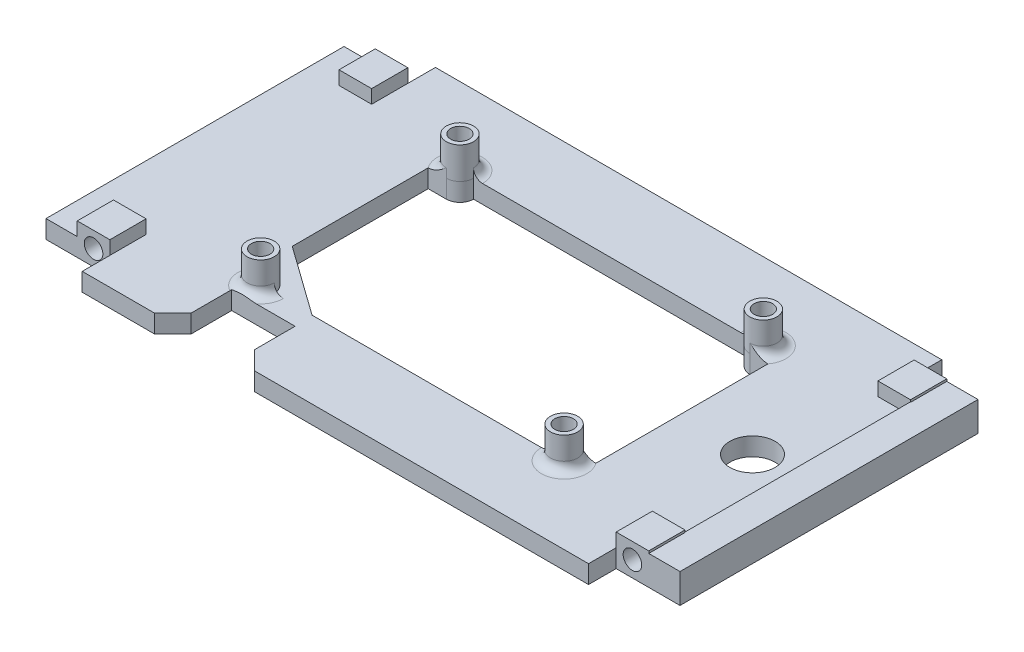
SolidWorks part; units mm, degrees
ref_plane "Front Plane" through (0, 0, 0) normal (0, 0, 1) x (1, 0, 0)
ref_plane "Top Plane" through (0, 0, 0) normal (0, 1, 0) x (1, 0, 0)
ref_plane "Right Plane" through (0, 0, 0) normal (1, 0, 0) x (0, 0, -1)
sketch "Sketch1" plane through (0, 0, 0) normal (0, 1, 0) x (1, 0, 0)
  line L0 (-70, -32.9) -> (-70, 32.9)
  line L1 (-70, -40) -> (70, -40) construction
  line L2 (-70, -40) -> (-70, 40) construction
  line L3 (-70, 40) -> (70, 40) construction
  line L4 (70, -40) -> (70, 40) construction
  line L5 (-70, -40) -> (70, 40) construction
  line L6 (-70, 40) -> (70, -40) construction
  line L7 (-70, 32.9) -> (-55.9, 32.9)
  line L8 (-55.9, 32.9) -> (-55.9, 40)
  line L9 (-55.9, 40) -> (55.9, 40)
  line L10 (55.9, 40) -> (55.9, 32.9)
  line L11 (55.9, 32.9) -> (70, 32.9)
  line L12 (70, 32.9) -> (70, -32.9)
  line L13 (70, -32.9) -> (55.9, -32.9)
  line L14 (55.9, -32.9) -> (55.9, -40)
  line L15 (55.9, -40) -> (-55.9, -40)
  line L16 (-55.9, -40) -> (-55.9, -32.9)
  line L17 (-55.9, -32.9) -> (-70, -32.9)
  point P0 (0, 0)
  dimension "D1" = 140
  dimension "D2" = 80
  dimension "D3" = 7.1
  dimension "D4" = 14.1
extrude "Boss-Extrude1" add sketch "Sketch1" along normal blind 4
sketch "Sketch3" plane through (0, 4, 0) normal (0, 1, 0) x (1, 0, 0)
  line L1 (-33.5, 22) -> (33.5, 22) construction
  line L2 (-33.5, 22) -> (-33.5, -22) construction
  line L3 (-33.5, -22) -> (33.5, -22) construction
  line L4 (33.5, 22) -> (33.5, -22) construction
  line L5 (-33.5, 22) -> (33.5, -22) construction
  line L6 (-33.5, -22) -> (33.5, 22) construction
  circle A0 centre (-33.5, -22) radius 3
  circle A1 centre (33.5, -22) radius 3
  circle A2 centre (33.5, 22) radius 3
  circle A3 centre (-33.5, 22) radius 3
  point P0 (0, 0)
  dimension "D4" = 6
  dimension "D1" = 67
  dimension "D2" = 44
sketch "Sketch2" plane through (0, 4, 0) normal (0, 1, 0) x (1, 0, 0)
  line L0 (-33.5, 19) -> (-30.5, 19)
  line L5 (-30.5, -22) -> (30.5, -22)
  line L6 (-33.5, -19) -> (-33.5, 19)
  line L7 (-30.5, 22) -> (30.5, 22)
  line L8 (33.5, -19) -> (33.5, 19)
  line L9 (-33.5, -22) -> (33.5, 22) construction
  line L10 (-33.5, 22) -> (33.5, -22) construction
  line L11 (-30.5, 19) -> (-30.5, 22)
  line L12 (30.5, 22) -> (30.5, 19)
  line L13 (30.5, 19) -> (33.5, 19)
  line L14 (33.5, -19) -> (30.5, -19)
  line L15 (30.5, -19) -> (30.5, -22)
  line L16 (-30.5, -22) -> (-30.5, -19)
  line L17 (-30.5, -19) -> (-33.5, -19)
  line L18 (33.5, -22) -> (-33.5, -22) construction
  line L19 (-33.5, -22) -> (-33.5, 22) construction
  line L20 (-33.5, 22) -> (33.5, 22) construction
  line L21 (33.5, 22) -> (33.5, -22) construction
  point P0 (0, 0)
  point P1 (0, 0)
  dimension "D1" = 3
extrude "Cut-Extrude1" cut sketch "Sketch2" against normal through all
extrude "Boss-Extrude2" add sketch "Sketch3" along normal blind 7
sketch "Sketch4" plane through (0, 11, 0) normal (0, 1, 0) x (1, 0, 0)
  circle A0 centre (-33.5, 22) radius 2.05
  circle A1 centre (33.5, 22) radius 2.05
  circle A2 centre (33.5, -22) radius 2.05
  circle A3 centre (-33.5, -22) radius 2.05
  dimension "D1" = 4.1
extrude "Cut-Extrude2" cut sketch "Sketch4" against normal through all and the other way through all
sketch "Sketch5" plane through (0, 4, 0) normal (0, 1, 0) x (1, 0, 0)
  line L0 (-33.5, -19) -> (-30.5, -19) construction
  line L1 (-33.5, 19) -> (-45.5, 19)
  line L2 (-33.5, 19) -> (-33.5, -19)
  line L3 (-33.5, -19) -> (-45.5, -19)
  line L4 (-45.5, 19) -> (-45.5, -19)
  line L5 (0, 22) -> (0, -22) construction
  line L6 (30.5, 22) -> (-30.5, 22) construction
  line L7 (-30.5, -22) -> (30.5, -22) construction
  line L8 (45.5, 19) -> (45.5, -19)
  line L9 (33.5, -19) -> (45.5, -19)
  line L10 (33.5, 19) -> (33.5, -19)
  line L11 (33.5, 19) -> (45.5, 19)
  dimension "D1" = 12
extrude "Cut-Extrude3" cut sketch "Sketch5" against normal through all
fillet "Fillet1" radius 3 4 edges at (30.5, 2, 19) (-30.5, 2, 19) (30.5, 2, -19) (-30.5, 2, -19)
sketch "Sketch7" plane through (0, 4, 0) normal (0, 1, 0) x (1, 0, 0)
  line L0 (0, 40) -> (0, -40) construction
  line L1 (55.9, 32.9) -> (63.1, 32.9)
  line L2 (55.9, 32.9) -> (55.9, 24.9)
  line L3 (55.9, 24.9) -> (63.1, 24.9)
  line L4 (63.1, 32.9) -> (63.1, 24.9)
  line L5 (55.9, 40) -> (-55.9, 40) construction
  line L6 (-55.9, -40) -> (55.9, -40) construction
  line L7 (-70, 0) -> (70, 0) construction
  line L8 (-70, 32.9) -> (-70, -32.9) construction
  line L9 (70, -32.9) -> (70, 32.9) construction
  dimension "D1" = 7.2
  dimension "D2" = 8
extrude "Boss-Extrude3" add sketch "Sketch7" along normal blind 3
sketch "Sketch8" plane through (0, 0, -32.9) normal (0, 0, -1) x (-1, 0, 0)
  line L0 (-63.1, 7) -> (-55.9, 0) construction
  circle A0 centre (-59.5, 3.5) radius 2.05
  dimension "D1" = 4.1
extrude "Cut-Extrude5" cut sketch "Sketch8" against normal blind 6
mirror "Mirror3" about plane through (0, 0, 0) normal (1, 0, 0) of "Cut-Extrude5", "Boss-Extrude3"
mirror "Mirror4" about plane through (0, 0, 0) normal (0, 0, 1) of "Mirror3"
sketch "Sketch10" plane through (0, 4, 0) normal (0, 1, 0) x (1, 0, 0)
  line L0 (55.9, 32.9) -> (55.9, 40) construction
  line L1 (-55.9, 40) -> (55.9, 40)
  line L2 (-55.9, 40) -> (-55.9, 39)
  line L3 (-55.9, 39) -> (55.9, 39)
  line L4 (55.9, 40) -> (55.9, 39)
  line L5 (-55.9, -32.9) -> (-55.9, -40) construction
  line L6 (55.9, -40) -> (-55.9, -40)
  line L7 (55.9, -40) -> (55.9, -39)
  line L8 (55.9, -39) -> (-55.9, -39)
  line L9 (-55.9, -40) -> (-55.9, -39)
  dimension "D1" = 1
  dimension "D2" = 1
extrude "Cut-Extrude7" cut sketch "Sketch10" against normal through all
fillet "Fillet5" radius 2 4 edges at (35.6213, 4, -24.1213) (35.6213, 4, 24.1213) (-35.6213, 4, 24.1213) (-35.6213, 4, -24.1213)
sketch "Sketch11" plane through (0, 4, 0) normal (0, 1, 0) x (1, 0, 0)
  line L1 (45.5, -19) -> (37.5, -19)
  line L2 (45.5, -19) -> (45.5, 19)
  line L3 (45.5, 19) -> (37.5, 19)
  line L4 (37.5, -19) -> (37.5, 19)
  line L5 (-37.5, -19) -> (-45.5, -19)
  line L6 (-37.5, -19) -> (-37.5, 19)
  line L7 (-37.5, 19) -> (-45.5, 19)
  line L8 (-45.5, -19) -> (-45.5, 19)
extrude "Boss-Extrude4" add sketch "Sketch11" against normal up to surface (4 mm away) up to face at (0, 0, 0)
sketch "Skizze3" plane through (0, 4, 0) normal (0, 1, 0) x (1, 0, 0)
  line L0 (37.5, 0) -> (70, 0) construction
  line L1 (37.5, 19) -> (37.5, -19) construction
  line L2 (70, -32.9) -> (70, 32.9) construction
  line L3 (63.1, 24.9) -> (63.1, -24.9) construction
  circle A0 centre (53.1, 0) radius 5
  dimension "D1" = 10
extrude "Schnitt-Linear austragen3" cut sketch "Skizze3" against normal up to surface (4 mm away) up to face at (0, 0, 0)
sketch "Skizze4" plane through (0, 4, 0) normal (0, 1, 0) x (1, 0, 0)
  line L0 (55.9, -39) -> (-55.9, -39) construction
  line L1 (-35.9, -39) -> (-21.9, -39)
  line L2 (-35.9, -39) -> (-35.9, -26)
  line L3 (-35.9, -26) -> (-21.9, -26)
  line L4 (-21.9, -39) -> (-21.9, -26)
  line L5 (-55.9, -32.9) -> (-55.9, -39) construction
  line L6 (-55.9, -32.9) -> (-55.9, -39) construction
  dimension "D1" = 13
  dimension "D2" = 20
  dimension "D3" = 14
extrude "Schnitt-Linear austragen5" cut sketch "Skizze4" along normal up to surface (7 mm away) from surface contours L1 L4 L3 L2 up to face at (-33.5, 11, 24.05) starting at face at (53.1, 0, -5)
chamfer "Fase1" distance 4 angle 45 2 edges at (-35.9, 2, 39) (-21.9, 2, 39)
sketch "Skizze5" plane through (0, 4, 0) normal (0, 1, 0) x (1, 0, 0)
  line L0 (-30.5, -22) -> (-22.1564, -22)
  line L1 (-28.5, -22) -> (28.5, -22) construction
  line L2 (-22.1564, -22) -> (-37.5, -11.025)
  line L3 (-37.5, -19) -> (-37.5, 19) construction
  line L4 (-37.5, -11.025) -> (-37.5, -19)
  line L5 (-37.5, -19) -> (-33.5, -19)
  arc A0 (-30.5, -22) -> (-33.5, -19) centre (-33.5, -22) ccw construction
  arc A1 (-30.5, -22) -> (-33.5, -19) centre (-33.5, -22) ccw
extrude "Aufsatz-Linear austragen1" add sketch "Skizze5" against normal up to surface (4 mm away) up to face at (53.1, 0, -5)
sketch "Skizze6" plane through (0, 4, 0) normal (0, 1, 0) x (1, 0, 0)
  line L1 (70, 32.9) -> (63, 32.9)
  line L2 (70, 32.9) -> (70, -32.9)
  line L3 (70, -32.9) -> (63, -32.9)
  line L4 (63, 32.9) -> (63, -32.9)
  point P7 (0, 0)
  dimension "D1" = 7
extrude "Aufsatz-Linear austragen2" add sketch "Skizze6" along normal blind 2.5
